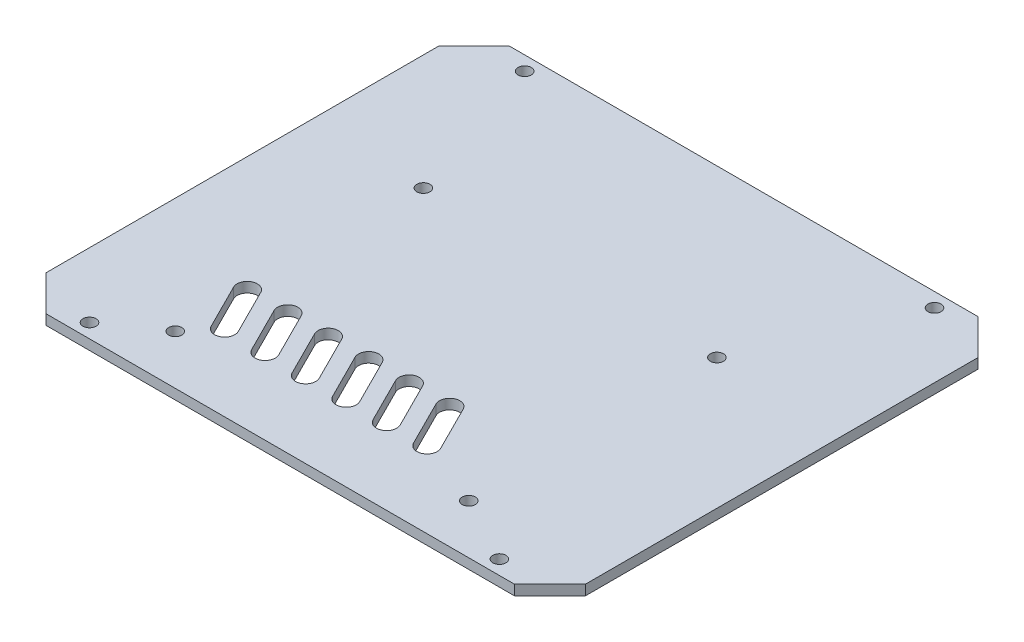
SolidWorks part; units mm, degrees
ref_plane "前视基准面" through (0, 0, 0) normal (0, 0, 1) x (1, 0, 0)
ref_plane "上视基准面" through (0, 0, 0) normal (0, 1, 0) x (1, 0, 0)
ref_plane "右视基准面" through (0, 0, 0) normal (1, 0, 0) x (0, 0, -1)
sketch "草图1" plane through (0, -21.39, 0) normal (0, -1, 0) x (1, 0, 0)
  line L16 (-61.8, -50.2958) -> (-54.7958, -57.3)
  line L17 (-54.7958, -57.3) -> (37.7958, -57.3)
  line L18 (37.7958, -57.3) -> (44.8, -50.2958)
  line L19 (44.8, -50.2958) -> (44.8, 27.2958)
  line L20 (44.8, 27.2958) -> (37.7958, 34.3)
  line L21 (-61.8, 27.2958) -> (-61.8, -50.2958)
  line L22 (37.7958, 34.3) -> (-54.7958, 34.3)
  line L23 (-54.7958, 34.3) -> (-61.8, 27.2958)
  line L24 (-61.8, -50.2958) -> (-54.7958, -57.3)
  line L25 (-54.7958, -57.3) -> (37.7958, -57.3)
  line L26 (37.7958, -57.3) -> (44.8, -50.2958)
  line L27 (44.8, -50.2958) -> (44.8, 27.2958)
  line L28 (44.8, 27.2958) -> (37.7958, 34.3)
  line L29 (-61.8, 27.2958) -> (-61.8, -50.2958)
  line L30 (37.7958, 34.3) -> (-54.7958, 34.3)
  line L31 (-54.7958, 34.3) -> (-61.8, 27.2958)
  dimension "D2" = 106.6
  dimension "D3" = 91.6
  dimension "D1" = 0.2
extrude "凸台-拉伸1" add sketch "草图1" along normal blind 2
sketch "草图2" plane through (0, -23.39, 0) normal (0, -1, 0) x (1, 0, 0)
  circle A0 centre (-39.0116, -24.5) radius 1.3
  circle A1 centre (19, -24.5) radius 1.3
  circle A2 centre (-39.0116, 24.5352) radius 1.3
  circle A3 centre (19, 24.5352) radius 1.3
  dimension "D1" = 2.6
extrude "切除-拉伸1" cut sketch "草图2" against normal up to next
sketch "草图3" plane through (0, -23.39, 0) normal (0, -1, 0) x (1, 0, 0)
  circle A0 centre (32, -54.5) radius 1.3 construction
  circle A1 centre (-49, -54.5) radius 1.3 construction
  circle A2 centre (32, 31.5) radius 1.3 construction
  circle A3 centre (-49, 31.5) radius 1.3 construction
  circle A4 centre (32, -54.5) radius 1.3
  circle A5 centre (-49, -54.5) radius 1.3
  circle A6 centre (32, 31.5) radius 1.3
  circle A7 centre (-49, 31.5) radius 1.3
extrude "切除-拉伸2" cut sketch "草图3" against normal up to next
sketch "草图4" plane through (0, -23.39, 0) normal (0, -1, 0) x (1, 0, 0)
  line L0 (-48.5377, 29.3811) -> (-45.4311, 23.1475) construction
  line L1 (-39.0282, 10.3) -> (-34.5444, 19.2384) construction
  line L2 (-40.8159, 11.1968) -> (-36.3321, 20.1352)
  line L3 (-37.2405, 9.4032) -> (-32.7567, 18.3417)
  line L5 (37.7958, 34.3) -> (-54.7958, 34.3) construction
  line L6 (-31.0282, 10.3) -> (-26.5444, 19.2384) construction
  line L9 (-32.8159, 11.1968) -> (-28.3321, 20.1352)
  line L12 (-29.2405, 9.4032) -> (-24.7567, 18.3417)
  line L15 (-23.0282, 10.3) -> (-18.5444, 19.2384) construction
  line L18 (-24.8159, 11.1968) -> (-20.3321, 20.1352)
  line L21 (-21.2405, 9.4032) -> (-16.7567, 18.3417)
  line L22 (-15.0282, 10.3) -> (-10.5444, 19.2384) construction
  line L23 (-16.8159, 11.1968) -> (-12.3321, 20.1352)
  line L24 (-13.2405, 9.4032) -> (-8.7567, 18.3417)
  line L25 (-7.0282, 10.3) -> (-2.5444, 19.2384) construction
  line L26 (-8.8159, 11.1968) -> (-4.3321, 20.1352)
  line L27 (-5.2405, 9.4032) -> (-0.7567, 18.3417)
  line L28 (0.9718, 10.3) -> (5.4556, 19.2384) construction
  line L29 (-0.8159, 11.1968) -> (3.6679, 20.1352)
  line L30 (2.7595, 9.4032) -> (7.2433, 18.3417)
  arc A0 (-40.8159, 11.1968) -> (-37.2405, 9.4032) centre (-39.0282, 10.3) ccw
  arc A1 (-32.7567, 18.3417) -> (-36.3321, 20.1352) centre (-34.5444, 19.2384) ccw
  arc A12 (-32.8159, 11.1968) -> (-29.2405, 9.4032) centre (-31.0282, 10.3) ccw
  arc A13 (-24.7567, 18.3417) -> (-28.3321, 20.1352) centre (-26.5444, 19.2384) ccw
  arc A14 (-24.8159, 11.1968) -> (-21.2405, 9.4032) centre (-23.0282, 10.3) ccw
  arc A15 (-16.7567, 18.3417) -> (-20.3321, 20.1352) centre (-18.5444, 19.2384) ccw
  arc A16 (-16.8159, 11.1968) -> (-13.2405, 9.4032) centre (-15.0282, 10.3) ccw
  arc A17 (-8.7567, 18.3417) -> (-12.3321, 20.1352) centre (-10.5444, 19.2384) ccw
  arc A18 (-8.8159, 11.1968) -> (-5.2405, 9.4032) centre (-7.0282, 10.3) ccw
  arc A19 (-0.7567, 18.3417) -> (-4.3321, 20.1352) centre (-2.5444, 19.2384) ccw
  arc A20 (-0.8159, 11.1968) -> (2.7595, 9.4032) centre (0.9718, 10.3) ccw
  arc A21 (7.2433, 18.3417) -> (3.6679, 20.1352) centre (5.4556, 19.2384) ccw
  point P6 (-36.7863, 14.7692)
  point P15 (-28.7863, 14.7692)
  point P22 (-20.7863, 14.7692)
  point P29 (-12.7863, 14.7692)
  point P36 (-4.7863, 14.7692)
  point P43 (3.2137, 14.7692)
  dimension "D1" = 2
  dimension "D2" = 10
  dimension "D3" = 8
  dimension "D4" = 12.8
  dimension "D5" = 24
  dimension "D6" = 6
extrude "切除-拉伸3" cut sketch "草图4" against normal up to next
sketch "草图5" plane through (0, -23.39, 0) normal (0, -1, 0) x (1, 0, 0)
sketch_block_instance "块1-1"
sketch_block "块1"
